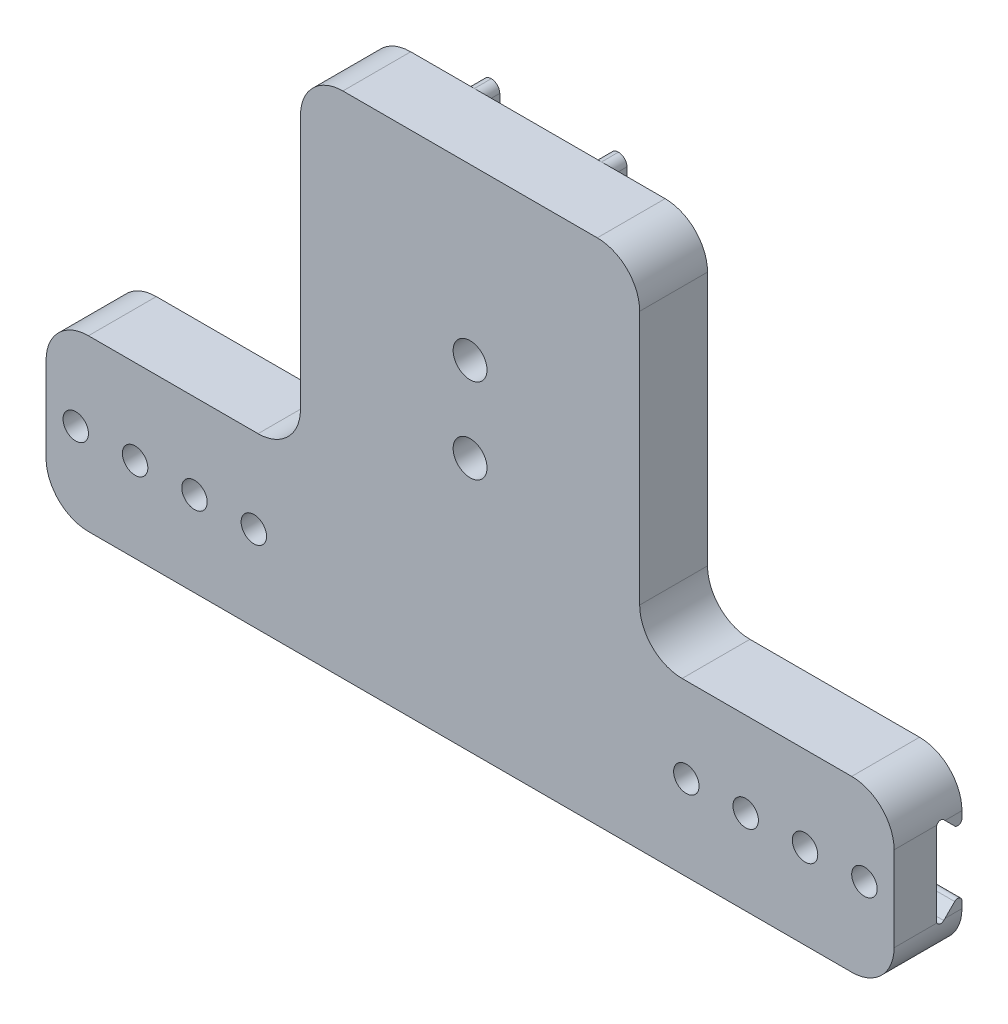
SolidWorks part; units mm, degrees
ref_plane "Front Plane" through (0, 0, 0) normal (0, 0, 1) x (1, 0, 0)
ref_plane "Top Plane" through (0, 0, 0) normal (0, 1, 0) x (1, 0, 0)
ref_plane "Right Plane" through (0, 0, 0) normal (1, 0, 0) x (0, 0, -1)
sketch "Sketch1" plane through (0, 0, 0) normal (0, 1, 0) x (1, 0, 0)
  line L1 (-20, 4) -> (20, 4)
  line L2 (-20, 4) -> (-20, -4)
  line L3 (-20, -4) -> (20, -4)
  line L4 (20, 4) -> (20, -4)
  line L5 (-20, 4) -> (20, -4) construction
  line L6 (-20, -4) -> (20, 4) construction
  point P0 (0, 0)
  dimension "D1" = 40
  dimension "D2" = 8
extrude "Boss-Extrude1" add sketch "Sketch1" against normal blind 60
sketch "Sketch2" plane through (20, 0, 0) normal (1, 0, 0) x (0, 0, -1)
  line L0 (-4, -60) -> (-4, 0) construction
  line L1 (4, -60) -> (-4, -60)
  line L2 (4, -60) -> (4, -40)
  line L3 (4, -40) -> (-4, -40)
  line L4 (-4, -60) -> (-4, -40)
  line L5 (0, -40) -> (0, -60) construction
  line L6 (4, -50) -> (-4, -50) construction
  point P532 (0, -50)
  dimension "D1" = 20
  dimension "D2" = 8
extrude "Boss-Extrude2" add sketch "Sketch2" along normal blind 30 contours L3 L4 L1 L2
sketch "Sketch3" plane through (50, 0, 0) normal (1, 0, 0) x (0, 0, -1)
  line L0 (1, -50) -> (1, -56)
  line L1 (1, -56) -> (4, -53)
  line L2 (4, -60) -> (4, -40) construction
  line L3 (1, -50) -> (1, -44)
  line L4 (1, -44) -> (4, -47)
  line L5 (4, -53) -> (4, -47)
  line L7 (4, -40) -> (-4, -40) construction
  dimension "D1" = 6
  dimension "D2" = 6
  dimension "D3" = 6
  dimension "D4" = 3
  dimension "D5" = 10
  dimension "D6" = 3
extrude "Cut-Extrude1" cut sketch "Sketch3" against normal blind 30 contours L0 L1 L5 L4 L3
sketch "Sketch6" plane through (0, 0, 4) normal (0, 0, 1) x (1, 0, 0)
  line L0 (50, -40) -> (20, -40) construction
  line L1 (50, -60) -> (50, -40) construction
  circle A0 centre (46.5, -50) radius 1.5
  dimension "D1" = 10
  dimension "D2" = 3
  dimension "D3" = 3.5
extrude "Cut-Extrude2" cut sketch "Sketch6" against normal through all contours A0
pattern_linear "LPattern1" count 4 spacing 7 along (-1, 0, 0) of "Cut-Extrude2"
mirror "Mirror3" about plane through (0, 0, 0) normal (1, 0, 0) of "LPattern1", "Cut-Extrude1", "Boss-Extrude2"
sketch "Sketch7" plane through (0, 0, 4) normal (0, 0, 1) x (1, 0, 0)
  circle A0 centre (0, -30) radius 2
  dimension "D1" = 30
extrude "Cut-Extrude3" cut sketch "Sketch7" against normal blind 30
sketch "Sketch8" plane through (0, 0, -4) normal (0, 0, -1) x (-1, 0, 0)
  line L0 (-20, 0) -> (20, 0) construction
  line L1 (-50, -60) -> (50, -60) construction
  line L2 (-8.5, 0) -> (-6.5, 0)
  line L3 (-8.5, 0) -> (-8.5, -60)
  line L4 (-8.5, -60) -> (-6.5, -60)
  line L5 (-6.5, 0) -> (-6.5, -60)
  line L6 (-7.5, -60) -> (-7.5, 0) construction
  line L7 (-8.5, -30) -> (-6.5, -30) construction
  line L9 (-20, -40) -> (-20, 0) construction
  point P662 (-7.5, -30)
  dimension "D1" = 2
  dimension "D2" = 12.5
extrude "Boss-Extrude3" add sketch "Sketch8" along normal blind 2
fillet "Fillet1" radius 1 2 edges at (8.5, 0, -5) (6.5, 0, -5)
mirror "Mirror4" about plane through (0, 0, 0) normal (1, 0, 0) of "Fillet1", "Boss-Extrude3"
fillet "Fillet2" radius 0.5 8 edges at (-35, -56, -1) (-35, -44, -1) (-35, -53, -4) (-35, -47, -4) (35, -44, -1) (35, -56, -1) (35, -53, -4) (35, -47, -4)
fillet "Fillet3" radius 5 8 edges at (-20, 0, 0) (20, 0, 0) (20, -40, 0) (-20, -40, 0) (-50, -60, 0) (-50, -40, 0) (50, -60, 0) (50, -40, 0)
sketch "Sketch9" plane through (0, 0, 4) normal (0, 0, 1) x (1, 0, 0)
  circle A0 centre (0, -20) radius 2
  circle A1 centre (0, -30) radius 2 construction
  dimension "D1" = 10
extrude "Cut-Extrude4" cut sketch "Sketch9" against normal blind 10 contours A0
